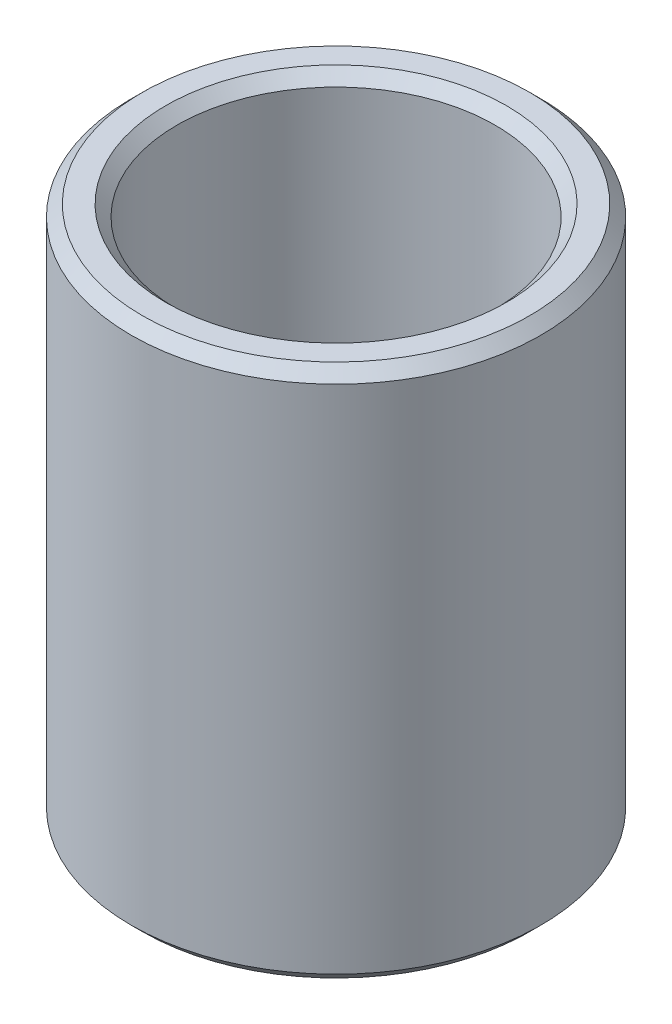
SolidWorks part; units mm, degrees
ref_plane "Front Plane" through (0, 0, 0) normal (0, 0, 1) x (1, 0, 0)
ref_plane "Top Plane" through (0, 0, 0) normal (0, 1, 0) x (1, 0, 0)
ref_plane "Right Plane" through (0, 0, 0) normal (1, 0, 0) x (0, 0, -1)
sketch "Sketch1" plane through (0, 0, 0) normal (0, 1, 0) x (1, 0, 0)
  circle A0 centre (0, 0) radius 30
  dimension "SLEEVE_OD" = 60
extrude "Boss-Extrude1" add sketch "Sketch1" along normal blind 78.1369
sketch "Sketch2" plane through (0, 0, 0) normal (0, 1, 0) x (1, 0, 0)
  circle A0 centre (0, 0) radius 23.3125
  dimension "BORE_D" = 46.625
extrude "Cut-Extrude1" cut sketch "Sketch2" along normal through all
chamfer "Chamfer1" distance 1.6489 angle 45 4 edges at (0, 78.1369, 23.3125) (0, 0, 23.3125) (0, 0, 30) (0, 78.1369, 30)
